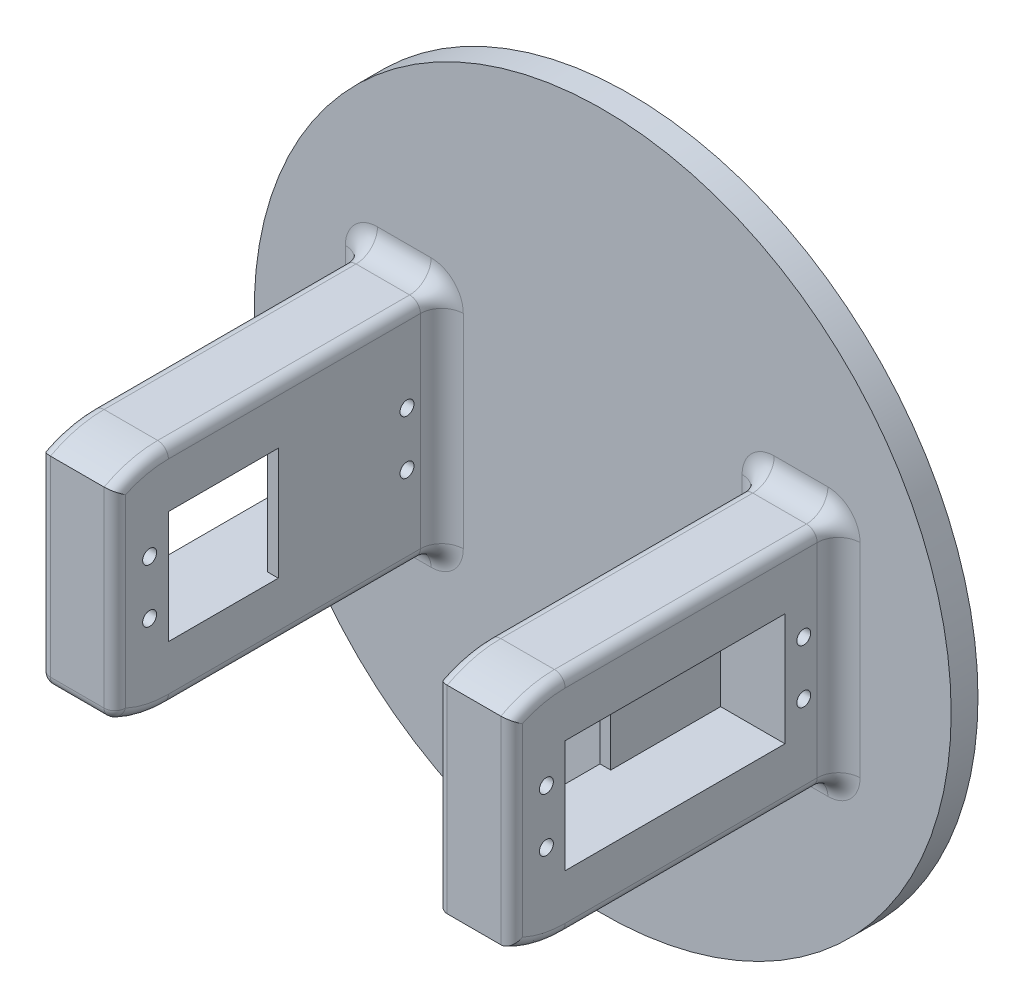
SolidWorks part; units mm, degrees
ref_plane "Front Plane" through (0, 0, 0) normal (0, 0, 1) x (1, 0, 0)
ref_plane "Top Plane" through (0, 0, 0) normal (0, 1, 0) x (1, 0, 0)
ref_plane "Right Plane" through (0, 0, 0) normal (1, 0, 0) x (0, 0, -1)
sketch "Sketch1" plane through (0, 0, 0) normal (0, 0, 1) x (1, 0, 0)
  circle A0 centre (0, 0) radius 65
  dimension "D1" = 130
extrude "Boss-Extrude1" add sketch "Sketch1" along normal blind 5
sketch "Sketch2" plane through (0, 0, 5) normal (0, 0, 1) x (1, 0, 0)
  line L0 (0, 88.8868) -> (0, -71.0654) construction
  line L1 (-44, 35) -> (-30, 35)
  line L2 (-44, 35) -> (-44, -35)
  line L3 (-44, -35) -> (-30, -35)
  line L4 (-30, 35) -> (-30, -35)
  line L5 (44, -35) -> (30, -35)
  line L6 (30, 35) -> (30, -35)
  line L7 (44, 35) -> (30, 35)
  line L8 (44, 35) -> (44, -35)
  dimension "D1" = 30
  dimension "D2" = 14
  dimension "D3" = 35
  dimension "D4" = 70
extrude "Boss-Extrude2" add sketch "Sketch2" along normal blind 70
sketch "Sketch4" plane through (-44, 0, 0) normal (-1, 0, 0) x (0, 0, 1)
  line L0 (5, 35) -> (5, -35) construction
  line L1 (15, -10.5) -> (56, -10.5)
  line L2 (15, -10.5) -> (15, 10.5)
  line L3 (15, 10.5) -> (56, 10.5)
  line L4 (56, -10.5) -> (56, 10.5)
  line L5 (15, -10.5) -> (56, 10.5) construction
  line L6 (15, 10.5) -> (56, -10.5) construction
  point P0 (35.5, 0)
  dimension "D1" = 10
  dimension "D2" = 41
  dimension "D3" = 21
extrude "Cut-Extrude1" cut sketch "Sketch4" against normal blind 12
sketch "Sketch5" plane through (-44, 0, 0) normal (-1, 0, 0) x (0, 0, 1)
  line L0 (5, 35) -> (5, -35) construction
  line L1 (5, 21) -> (56, 21)
  line L2 (5, 21) -> (5, -21)
  line L3 (5, -21) -> (56, -21)
  line L4 (56, 21) -> (56, -21)
  line L5 (56, -10.5) -> (56, 10.5) construction
  line L6 (75, 35) -> (5, 35) construction
  line L7 (75, -35) -> (5, -35) construction
  line L9 (66, 18.4662) -> (66, -18.4662)
  line L13 (5, 35) -> (5, -35)
  line L14 (5, -35) -> (75, -35)
  line L15 (75, -35) -> (75, 35)
  line L16 (75, 35) -> (5, 35)
  line L17 (5, 35) -> (5, -35)
  line L18 (5, -35) -> (75, -35)
  line L19 (75, -35) -> (75, 35)
  line L20 (75, 35) -> (5, 35)
  arc A0 (75, 8.9443) -> (75, -8.9443) centre (56, 0) ccw
  line M10 (5, 35) -> (5, -35)
  line M11 (5, -35) -> (75, -35)
  line M12 (75, -35) -> (75, 35)
  line M13 (75, 35) -> (5, 35)
  dimension "D1" = 14
  dimension "D2" = 14
  dimension "D4" = 10
  dimension "D3" = 0
extrude "Cut-Extrude2" cut sketch "Sketch5" against normal up to next contours A0 L3 M10 M11 M12 | A0 L1 M12 M13 M10 | L9 A0 L19 region at (-44, 27.3606, 41.8924) region at (-44, -27.3606, 41.8924) region at (-44, 0, 70.0363)
fillet "Fillet1" radius 2 11 edges at (-30, 20.3567, 61.158) (-30, -20.3567, 61.158) (-44, -20.3567, 61.158) (-44, 21, 30.5) (-30, 0, 66) (-30, 21, 30.5) (-30, -21, 30.5) (-44, -21, 30.5) (-44, 20.3567, 61.158) (-37, -18.4662, 66) (-44, 0, 66)
fillet "Fillet2" radius 4 8 edges at (-43.4142, 20.4142, 5) (-37, 21, 5) (-30.5858, 20.4142, 5) (-30, 0, 5) (-30.5858, -20.4142, 5) (-37, -21, 5) (-43.4142, -20.4142, 5) (-44, 0, 5)
mirror "Mirror2" about plane through (0, 0, 0) normal (1, 0, 0) of "Cut-Extrude1"
mirror "Mirror3" about plane through (0, 0, 0) normal (1, 0, 0) of "Cut-Extrude2"
fillet "Fillet3" radius 2 10 edges at (30, 20.3567, 61.158) (30, -20.3567, 61.158) (44, 20.3567, 61.158) (44, -20.3567, 61.158) (30, 21, 30.5) (30, -21, 30.5) (30, 0, 66) (44, 21, 30.5) (44, 0, 66) (44, -21, 30.5)
fillet "Fillet4" radius 4 8 edges at (43.4142, -20.4142, 5) (37, -21, 5) (30.5858, -20.4142, 5) (30, 0, 5) (30.5858, 20.4142, 5) (37, 21, 5) (43.4142, 20.4142, 5) (44, 0, 5)
sketch "Sketch7" plane through (-44, 0, 0) normal (-1, 0, 0) x (0, 0, 1)
  line L0 (71.8559, 0) -> (-5.9033, 0) construction
  line L1 (56, -10.5) -> (56, 10.5) construction
  line L2 (35.5, 19) -> (35.5, -19) construction
  line L3 (56, 19) -> (9, 19) construction
  line L4 (9, -19) -> (56, -19) construction
  line L5 (15, 10.5) -> (15, -10.5) construction
  circle A0 centre (59.5, 5) radius 1.3
  circle A1 centre (59.5, -5) radius 1.3
  circle A2 centre (11.5, -5) radius 1.3
  circle A3 centre (11.5, 5) radius 1.3
  dimension "D1" = 2.6
  dimension "D2" = 3.5
  dimension "D3" = 5
extrude "Cut-Extrude3" cut sketch "Sketch7" against normal up to next
mirror "Mirror6" about plane through (0, 0, 0) normal (1, 0, 0) of "Cut-Extrude3"
sketch "Sketch8" plane through (-32, 0, 0) normal (-1, 0, 0) x (0, 0, 1)
  line L0 (15, -10.5) -> (56, -10.5) construction
  line L1 (56, 10.5) -> (35.5, 10.5)
  line L2 (56, 10.5) -> (56, -10.5)
  line L3 (56, -10.5) -> (35.5, -10.5)
  line L4 (35.5, 10.5) -> (35.5, -10.5)
extrude "Cut-Extrude4" cut sketch "Sketch8" against normal up to next
mirror "Mirror7" about plane through (0, 0, 0) normal (1, 0, 0) of "Cut-Extrude4"
